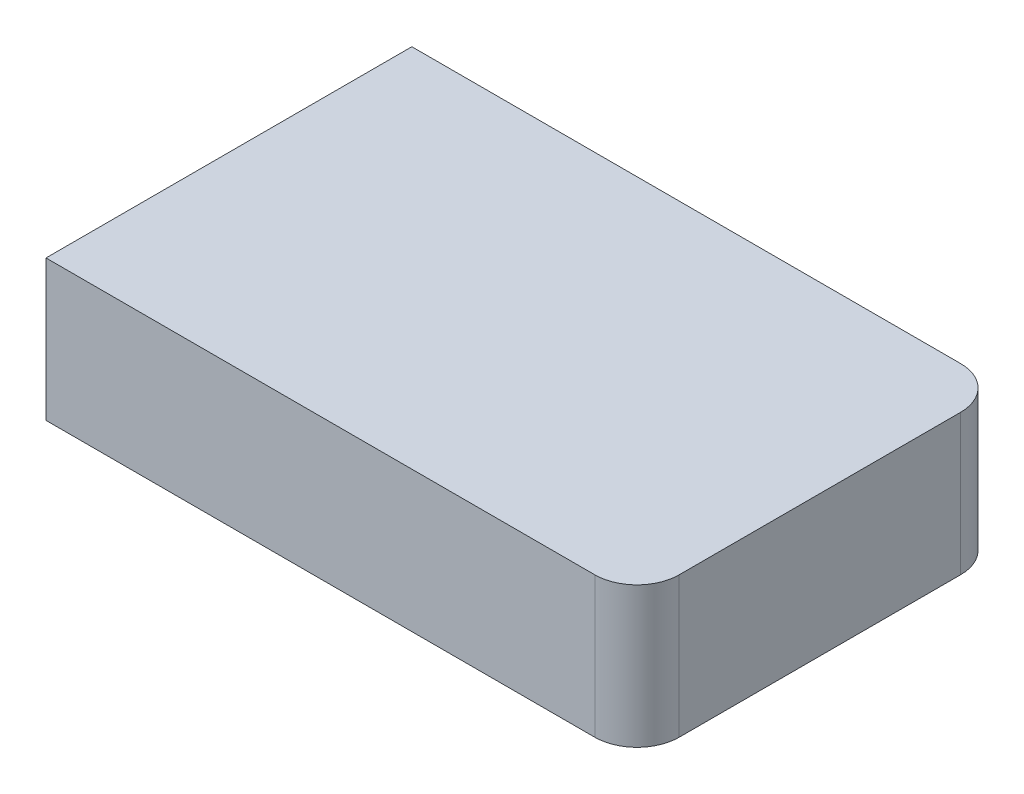
SolidWorks part; units mm, degrees
ref_plane "前视基准面" through (0, 0, 0) normal (0, 0, 1) x (1, 0, 0)
ref_plane "上视基准面" through (0, 0, 0) normal (0, 1, 0) x (1, 0, 0)
ref_plane "右视基准面" through (0, 0, 0) normal (1, 0, 0) x (0, 0, -1)
sketch "草图1" plane through (0, 0, 0) normal (0, 1, 0) x (1, 0, 0)
  line L1 (-21, 13) -> (21, 13)
  line L2 (-21, 13) -> (-21, -13)
  line L3 (-21, -13) -> (21, -13)
  line L4 (21, 13) -> (21, -13)
  line L5 (-21, 13) -> (21, -13) construction
  line L6 (-21, -13) -> (21, 13) construction
  point P0 (0, 0)
  dimension "D1" = 42
  dimension "D2" = 26
extrude "凸台-拉伸1" add sketch "草图1" along normal blind 10
fillet "圆角1" radius 3 2 edges at (21, 5, -13) (21, 5, 13)
